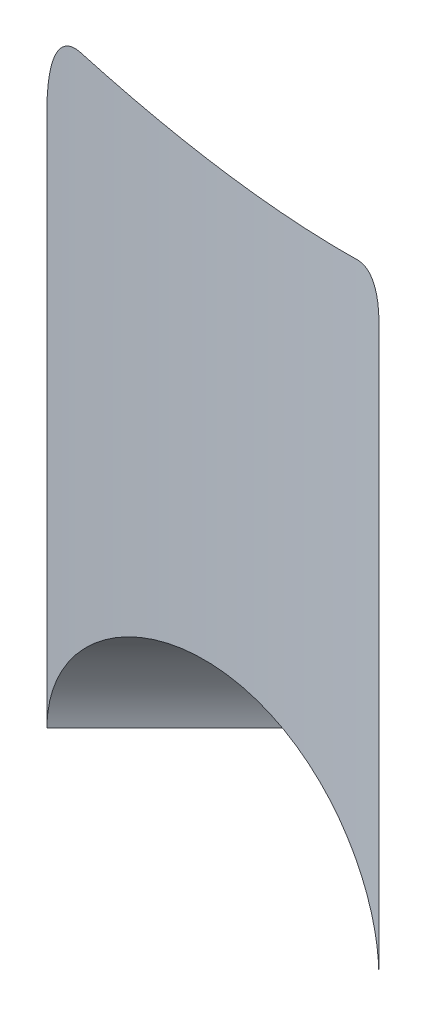
SolidWorks part; units mm, degrees
ref_plane "Front Plane" through (0, 0, 0) normal (0, 0, 1) x (1, 0, 0)
ref_plane "Top Plane" through (0, 0, 0) normal (0, 1, 0) x (1, 0, 0)
ref_plane "Right Plane" through (0, 0, 0) normal (1, 0, 0) x (0, 0, -1)
sketch "Sketch1" plane through (0, 0, 0) normal (0, 1, 0) x (1, 0, 0)
  line L0 (0, 0) -> (-8.9803, -8.9803)
  line L1 (-8.9803, -8.9803) -> (8.9803, -8.9803)
  line L2 (8.9803, -8.9803) -> (0, 0)
  dimension "D1" = 12.7
extrude "Boss-Extrude1" add sketch "Sketch1" along normal blind 25.4
sketch "Sketch2" plane through (0, 0, 0) normal (0.7071, 0, -0.7071) x (-0.7071, 0, -0.7071)
  line L1 (-12.7, 0) -> (0, 0) construction
  circle A0 centre (-6.35, 0) radius 6.35
  dimension "D1" = 12.7
extrude "Cut-Extrude3" cut sketch "Sketch2" against normal up to next
ref_axis "Axis1" through (-1.6662, 0, 10.6464) along (0.7071, 0, -0.7071)
sketch "Sketch5" plane through (0, 25.4, 0) normal (0, 1, 0) x (1, 0, 0)
  line L0 (-16.8869, -25.8671) -> (24.7669, 15.7867) construction
  circle A0 centre (-9.8382, -90.6605) radius 83.82
  dimension "D2" = 167.64
  dimension "D1" = 50.8
extrude "Cut-Extrude4" cut sketch "Sketch5" against normal through all
ref_point "Point1"
ref_point "Point2"
ref_point "Point3"
ref_point "Point4"
ref_point "Point5"
ref_plane "Plane2" through (0.1779, 0.4984, -1.3527) normal (-0.1225, -0.3431, 0.9313) x (0.9925, -0.0424, 0.115)
sketch "Sketch6" plane through (0.1779, 0.4984, -1.3527) normal (-0.1225, -0.3431, 0.9313) x (0.9925, -0.0424, 0.115)
  line L1 (8.8691, 3.9723) -> (-7.1239, 3.9723)
  line L2 (8.8691, 3.9723) -> (8.8691, 26.9384)
  line L3 (8.8691, 26.9384) -> (-7.1239, 26.9384)
  line L4 (-7.1239, 3.9723) -> (-7.1239, 26.9384)
  line L5 (-1.0758, 23.8337) -> (0, 0) construction
  point P4 (-0.1793, 3.9723)
extrude "Cut-Extrude5" cut sketch "Sketch6" against normal up to next
fillet "Fillet1" radius 2.54 2 edges at (-3.4461, 14.8167, 3.4461) (4.4901, 14.8167, 4.4901)
